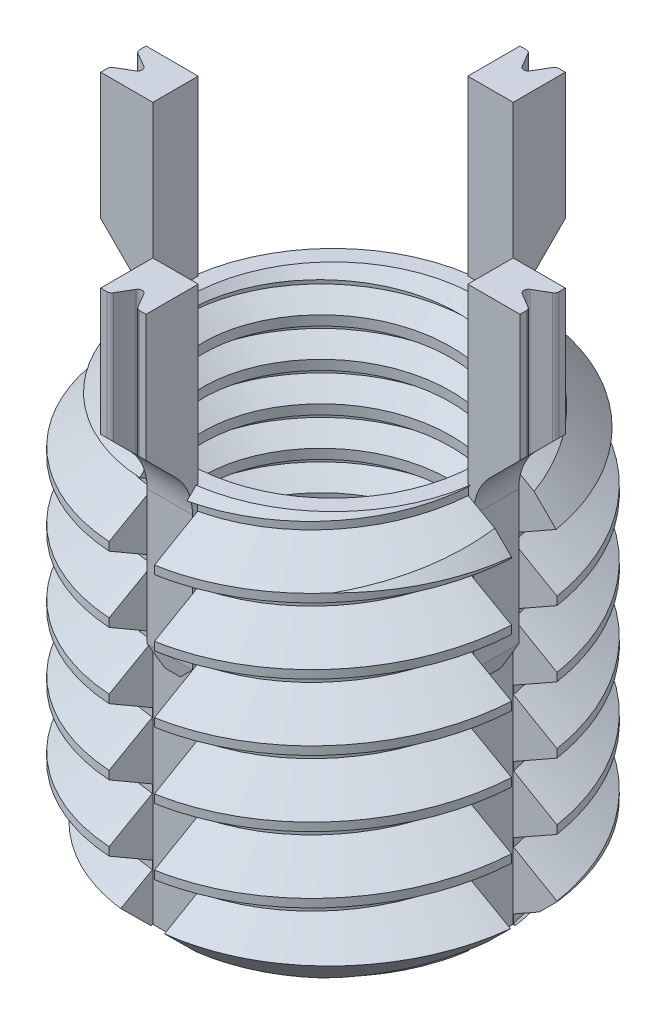
SolidWorks part; units mm, degrees
note: '?' marks a value the reader was unsure of.
material "AISI 316 Annealed Stainless Steel Bar (SS)"
ref_plane "Front Plane" through (0, 0, 0) normal (0, 0, 1) x (1, 0, 0)
ref_plane "Top Plane" through (0, 0, 0) normal (0, 1, 0) x (1, 0, 0)
ref_plane "Right Plane" through (0, 0, 0) normal (1, 0, 0) x (0, 0, -1)
sketch "Sketch1" plane through (0, 0, 0) normal (0, 1, 0) x (1, 0, 0)
  circle A0 centre (0, 0) radius 5.5626 construction
  circle A1 centre (0, 0) radius 3.9751 construction
  circle A2 centre (0, 0) radius 5.0927 construction
  dimension "For Maximum Hole Diameter" = 10.1854
  dimension "For Tap Thread Size" = 11.1252
  dimension "Thread Size" = 7.9502
sketch "Sketch2" plane through (0, 0, 0) normal (0, 0, 1) x (1, 0, 0)
  line L0 (0, 0) -> (0, -11.0998) construction
  line L1 (0, 4.7561) -> (0, -4.7561) construction
  line L2 (0, 0) -> (-1.8143, 0)
  line L3 (0, 0) -> (1.0583, 0)
  point P5 (0, 0)
  dimension "D1" = 9.5123
  dimension "External Pitch" = 1.8143
  dimension "Internal Pitch" = 1.0583
  dimension "Installed Length" = 11.0998
  dimension "For Minimum Material Thickness" = 11.0998
ref_axis "Axis1" through (0, 5.5761, 0) along (0, -1, 0)?
sketch "Sketch3" plane through (0, 0, 0) normal (0, 1, 0) x (1, 0, 0)
  circle A0 centre (0, 0) radius 5.5626 construction
  circle A1 centre (0, 0) radius 5.5626
extrude "Extrude1" add sketch "Sketch3" against normal up to vertex (11.0998 mm away) up to point (0, -11.0998, 0)
sketch "Sketch6" plane through (0, 0, 0) normal (0, 1, 0) x (1, 0, 0)
  circle A0 centre (0, 0) radius 3.9751 construction
  circle A1 centre (0, 0) radius 3.9751
extrude "Extrude3" cut sketch "Sketch6" against normal through all
sketch "Sketch4" plane through (0, 0, 0) normal (0, 1, 0) x (1, 0, 0)
  circle A1 centre (0, 0) radius 5.5626
  circle A2 centre (0, 0) radius 5.5626
  point P0 (-5.5626, 0)
  dimension "D1" = 0
chamfer "Chamfer1" distance 1.1339 angle 45 2 edges at (0, -11.0998, 5.5626) (0, 0, 5.5626)
sketch "Outer Thread Profile" plane through (0, 0, 0) normal (0, 0, 1) x (1, 0, 0)
  line L0 (-5.759, 1.7009) -> (-5.759, -0.1134) construction
  line L1 (-5.759, -0.1134) -> (-4.1878, 0.7938) construction
  line L2 (-4.1878, 0.7938) -> (-5.759, 1.7009) construction
  line L3 (-5.759, 0.7938) -> (-5.5626, 0.7938) construction
  line L4 (-5.5626, 0.7938) -> (-4.5806, 0.7938) construction
  line L5 (-4.3842, 0.7938) -> (-4.1878, 0.7938) construction
  line L6 (-5.5626, 1.5875) -> (-5.5626, 0) construction
  line L7 (-4.3842, 0.9071) -> (-4.3842, 0.6804) construction
  line L12 (-4.5806, 0.7938) -> (-4.3842, 0.7938) construction
  point P10 (-5.6608, 0.7938)
  point P17 (-4.4824, 0.7938)
  dimension "D1" = 1.8143
  dimension "D2" = 0.2268
sketch "Sketch11" plane through (0, 0, 0) normal (0, 1, 0) x (1, 0, 0)
  line L0 (-5.5626, 0.6237) -> (-4.4824, 0.6237)
  line L1 (-4.4824, 0.6237) -> (-4.3265, 0.6237)
  line L2 (-4.4824, 0.6237) -> (-4.4824, -0.6237) construction
  line L3 (-4.4824, -0.6237) -> (-4.3265, -0.6237)
  line L4 (-4.3265, 0.6237) -> (-4.3265, -0.6237)
  line L6 (-5.5626, 0.6237) -> (-5.5626, -0.6237)
  line L7 (-5.5626, -0.6237) -> (-4.4824, -0.6237)
  line L9 (-5.5626, 0) -> (-4.4824, 0) construction
  line L10 (-4.4824, 0) -> (-4.3265, 0) construction
  circle A1 centre (0, 0) radius 5.5626 construction
  dimension "D1" = 1.2473
  dimension "D2" = 0.1559
extrude "Extrude2" cut sketch "Sketch11" against normal through all
pattern_circular "CirPattern1" count 4 over 360 about axis through (0, 0, 0) along (0, 1, 0) of "Extrude2"
sketch "Sketch12" plane through (0, 0, 0) normal (0, 1, 0) x (1, 0, 0)
  line L1 (-4.4824, 0.6237) -> (-4.3265, 0.6237)
  line L2 (-4.4824, 0.6237) -> (-4.4824, -0.6237)
  line L3 (-4.4824, -0.6237) -> (-4.3265, -0.6237)
  line L4 (-4.3265, 0.6237) -> (-4.3265, -0.6237)
extrude "Extrude6" add sketch "Sketch12" along normal up to vertex (4.7561 mm away) and the other way up to vertex (4.7561 mm away) separate body up to point (0, 4.7561, 0) other way up to point (0, -4.7561, 0)
sketch "Sketch13" plane through (0, 4.7561, 0) normal (0, 1, 0) x (1, 0, 0)
  line L0 (-5.759, 0) -> (-4.4824, 0) construction
  line L1 (-5.759, 0.6237) -> (-4.4824, 0.6237)
  line L2 (-5.759, 0.6237) -> (-5.759, -0.6237)
  line L3 (-5.759, -0.6237) -> (-4.4824, -0.6237)
  line L4 (-4.4824, 0.6237) -> (-4.4824, -0.6237)
  line L5 (-5.759, 0) -> (-5.5626, 0) construction
  line L6 (-5.5626, 0.6237) -> (-4.4824, 0.6237) construction
extrude "Extrude7" add sketch "Sketch13" against normal up to surface (4.7561 mm away) up to plane "Top Plane"
sketch "Sketch18" plane through (0, 4.7561, 0) normal (0, 1, 0) x (1, 0, 0)
  line L0 (-5.759, 0.3742) -> (-5.1207, 0)
  line L1 (-5.1207, 0) -> (-5.759, -0.3742)
  line L2 (-5.759, -0.3742) -> (-5.759, 0.3742)
  line L3 (-5.759, 0.6237) -> (-5.759, -0.6237) construction
  line L4 (-5.759, 0) -> (-4.4824, 0) construction
  dimension "D1" = 0.7484
extrude "Cut-Extrude1" cut sketch "Sketch18" against normal up to surface (4.7561 mm away) up to face at (-5.1207, 0, -0.1559)
fillet "Fillet1" radius 0.1247 3 edges at (-5.1207, 2.3781, 0) (-5.759, 2.3781, 0.3742) (-5.759, 2.3781, -0.3742)
sketch "Sketch14" plane through (0, 0, 0) normal (0, 0, 1) x (1, 0, 0)
  line L0 (-5.759, 0) -> (-5.759, 1.2766)
  line L1 (-5.759, 0) -> (-5.759, 4.7561) construction
  line L2 (-5.759, 1.2766) -> (-4.4824, 0)
  line L4 (-4.4824, 0) -> (-5.759, 0)
extrude "Extrude8" cut sketch "Sketch14" against normal through all and the other way through all
sketch "Sketch15" plane through (-4.4824, 0, 0) normal (-1, 0, 0) x (0, 0, 1)
  line L0 (-0.6237, 1.2766) -> (-0.6237, -4.7561) construction
  line L1 (-0.6237, -4.7561) -> (0.6237, -4.7561) construction
  line L2 (-0.6237, -4.7561) -> (-0.6237, -4.3442)
  line L3 (-0.6237, 0) -> (-0.6237, -4.7561) construction
  line L4 (-0.6237, -4.3442) -> (-0.2117, -4.7561)
  line L5 (-0.2117, -4.7561) -> (-0.6237, -4.7561)
  line L6 (0.6237, 1.2766) -> (0.6237, -4.7561) construction
  line L8 (0.6237, -4.7561) -> (0.6237, -4.3442)
  line L9 (0.6237, 0) -> (0.6237, -4.7561) construction
  line L10 (0.6237, -4.3442) -> (0.2117, -4.7561)
  line L11 (-0.6237, -4.3442) -> (0.6237, -4.3442) construction
  line L12 (0.2117, -4.7561) -> (0.6237, -4.7561)
  line L13 (-0.6237, -1.1339) -> (-0.6237, -9.9659) construction
  dimension "D1" = 45
  dimension "D2" = 0.4233
extrude "Extrude9" cut sketch "Sketch15" against normal through all
sketch "Sketch19" plane through (0, 0, 0.6237) normal (0, 0, -1) x (-1, 0, 0)
  line L0 (4.4824, -4.3442) -> (4.4044, -4.7561)
  line L1 (4.4824, -4.7561) -> (4.3265, -4.7561) construction
  line L2 (4.4044, -4.7561) -> (4.4824, -4.7561)
  line L3 (4.4824, -4.7561) -> (4.4824, -4.3442)
extrude "Cut-Extrude2" cut sketch "Sketch19" along normal up to surface (1.2473 mm away)
fillet "Fillet2" radius 1.5875 4 edges
pattern_circular "CirPattern2" count 4 over 360 about axis through (0, 0, 0) along (0, 1, 0) of bodies 124 114
sketch "For Drawing" plane through (0, 0, 0) normal (0, 0, 1) x (1, 0, 0)
  line L0 (5.5626, 0) -> (5.5626, -11.0998) construction
  point P0 (-5.5626, -3.6286)
  dimension "D1" = 5.5626
  dimension "D2" = 3.6286
curve "Helix/Spiral1" pitch 1.8143 height 12.9141 turns 7.118 parameters "Height"=12.9141, "External Pitch"=1.8143
sketch "Sketch17" plane through (0, 0, 0) normal (0, 0, 1) x (1, 0, 0)
  line L0 (-5.6608, 1.6442) -> (-5.6608, -0.0567)
  line L1 (-4.1878, 0.7938) -> (-5.759, 1.7009) construction
  line L2 (-5.759, -0.1134) -> (-4.1878, 0.7938) construction
  line L3 (-5.6608, -0.0567) -> (-4.3842, 0.6804)
  line L4 (-4.3842, 0.6804) -> (-4.3842, 0.9071)
  line L5 (-4.3842, 0.9071) -> (-5.6608, 1.6442)
sweep "Cut-Sweep1" cut profiles "Sketch17" path "Helix/Spiral1"
sketch "Sketch7" plane through (0, 0, 0) normal (0, 1, 0) x (1, 0, 0)
  circle A0 centre (0, 0) radius 3.9751 construction
  circle A1 centre (0, 0) radius 3.9751
  circle A2 centre (0, 0) radius 3.9751 construction
  point P3 (0, -3.9751)
curve "Helix/Spiral2" pitch 1.0583 height 12.1581 turns 11.488 parameters "Height"=12.1581, "Internal Pitch"=1.0583
sketch "Sketch8" plane through (0, 0, 0) normal (-1, 0, 0) x (0, 0, 1)
  line L0 (4.0897, 0.9922) -> (4.0897, -0.0661) construction
  line L1 (4.0897, -0.0661) -> (3.1731, 0.463) construction
  line L2 (3.1731, 0.463) -> (4.0897, 0.9922) construction
  line L3 (3.9751, 0.926) -> (3.9751, 0)
  line L4 (3.2877, 0.3969) -> (3.2877, 0.5292) construction
  line L5 (4.0897, 0.463) -> (3.9751, 0.463) construction
  line L6 (3.9751, 0.463) -> (3.4023, 0.463) construction
  line L7 (3.2877, 0.463) -> (3.1731, 0.463) construction
  line L8 (3.4023, 0.5953) -> (3.9751, 0.926)
  line L10 (3.9751, 0) -> (3.4023, 0.3307)
  line L11 (3.4023, 0.5953) -> (3.4023, 0.3307)
  line L12 (3.2877, 0.463) -> (3.4023, 0.463) construction
  dimension "D1" = 1.0583
  dimension "D2" = 0.1323
sweep "Sweep1" add profiles "Sketch8" path "Helix/Spiral2"
sketch "Sketch9" plane through (0, 0, 0) normal (0, 1, 0) x (1, 0, 0)
  circle A1 centre (0, 0) radius 3.9751
  circle A2 centre (0, 0) radius 3.9751
  dimension "D1" = 0
extrude "Extrude4" cut sketch "Sketch9" against normal through all draft 45 and the other way through all draft 45
sketch "Sketch10" plane through (0, -11.0998, 0) normal (0, -1, 0) x (1, 0, 0)
  circle A1 centre (0, 0) radius 3.9751
  circle A2 centre (0, 0) radius 3.9751
  dimension "D1" = 0
extrude "Extrude5" cut sketch "Sketch10" against normal through all draft 45 and the other way through all draft 45
equation "\"Height@Helix/Spiral1\" = \"External Pitch@Sketch2\" + \"Installed Length@Sketch2\""
equation "\"D1@Outer Thread Profile\"=\"External Pitch@Sketch2\""
equation "\"D2@Outer Thread Profile\" = \"D1@Outer Thread Profile\" / 8"
equation "\"D1@Chamfer1\" = \"External Pitch@Sketch2\" * 5 / 8"
equation "\"Height@Helix/Spiral2\"=\"Internal Pitch@Sketch2\" + \"Installed Length@Sketch2\""
equation "\"D1@Sketch8\"=\"Internal Pitch@Sketch2\""
equation "\"D2@Sketch8\" = \"D1@Sketch8\" / 8"
equation "\"D1@CirPattern2\" = \"Number of Keys@CirPattern1\""
equation "\"D1@Sketch11\" = \"External Pitch@Sketch2\" * 11 / 16"
equation "\"D2@Sketch11\" = \"D1@Sketch11\" * 1 / 8"
equation "\"D1@Sketch2\" = \"Installed Length@Sketch2\" - ( 1 / 16 )"
equation "\"D1@For Drawing\" = \"For Tap Thread Size@Sketch1\" / 2"
equation "\"D2@For Drawing\"= \"External Pitch@Sketch2\" * 2"
equation "\"External Pitch@Helix/Spiral1\"=\"External Pitch@Sketch2\""
equation "\"Internal Pitch@Helix/Spiral2\"=\"Internal Pitch@Sketch2\""
equation "\"D1@Sketch18\"=\"D1@Sketch11\"*.6"
equation "\"D1@Fillet1\"=\"D1@Sketch11\"*.1"
equation "\"D2@Sketch15\"=\"Internal Pitch@Sketch2\"*.40"
equation "\"D1@Fillet2\"=\"Internal Pitch@Sketch2\"*1.5"
